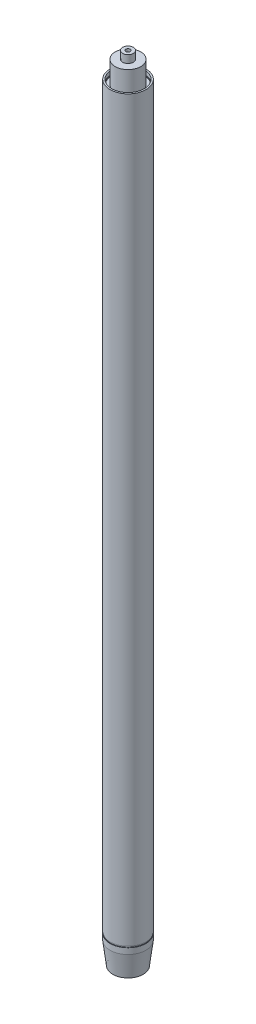
SolidWorks part; units mm, degrees
ref_plane "Front Plane" through (0, 0, 0) normal (0, 0, 1) x (1, 0, 0)
ref_plane "Top Plane" through (0, 0, 0) normal (0, 1, 0) x (1, 0, 0)
ref_plane "Right Plane" through (0, 0, 0) normal (1, 0, 0) x (0, 0, -1)
sketch "Sketch1" plane through (0, 0, 0) normal (0, 1, 0) x (1, 0, 0)
  circle A0 centre (0, 0) radius 26.7208
  circle A1 centre (0, 0) radius 24.3332
  dimension "D1" = 53.4416
  dimension "D2" = 2.3876
extrude "Boss-Extrude1" add sketch "Sketch1" along normal blind 1111.25
sketch "Sketch2" plane through (0, 0, 0) normal (0, 0, 1) x (1, 0, 0)
  line L0 (-26.7208, 0) -> (26.7208, 0) construction
  line L1 (22.5552, 7.112) -> (25.0952, 7.112)
  line L2 (22.5552, 7.112) -> (22.5552, 5.08)
  line L3 (22.5552, 5.08) -> (25.0952, 5.08)
  line L4 (25.0952, 7.112) -> (25.0952, 5.08)
  line L5 (24.3332, 0) -> (24.3332, 1111.25) construction
  dimension "D1" = 5.08
  dimension "D2" = 2.032
  dimension "D3" = 0.762
  dimension "D4" = 2.54
ref_axis "Axis1" through (0, 1111.25, 0) along (0, -1, 0)
revolve "Cut-Revolve1" cut sketch "Sketch2" angle 360 about axis through (0, 1111.25, 0) along (0, -1, 0)
ref_plane "Plane1" through (0, 555.625, 0) normal (0, -1, 0) x (-1, 0, 0)
mirror "Mirror1" about plane through (0, 555.625, 0) normal (0, -1, 0) of "Cut-Revolve1"
sketch "Sketch3" plane through (0, 0, 0) normal (1, 0, 0) x (0, 0, -1)
  line L0 (-26.7208, 0) -> (26.7208, 0) construction
  line L1 (25.9588, 10.795) -> (27.2288, 10.795)
  line L2 (25.9588, 10.795) -> (25.9588, 8.763)
  line L3 (25.9588, 8.763) -> (27.2288, 8.763)
  line L4 (27.2288, 10.795) -> (27.2288, 8.763)
  line L5 (26.7208, 0) -> (26.7208, 1111.25) construction
  dimension "D1" = 10.795
  dimension "D2" = 2.032
  dimension "D3" = 1.27
  dimension "D4" = 0.762
revolve "Cut-Revolve2" cut sketch "Sketch3" angle 360 about axis through (0, 1111.25, 0) along (0, -1, 0)
sketch "Sketch4" plane through (0, 0, 0) normal (0, 0, 1) x (1, 0, 0)
  line L0 (26.7208, 0) -> (22.6695, -33.147)
  line L1 (24.3332, 0) -> (20.2819, -33.147)
  line L2 (22.6695, -33.147) -> (20.2819, -33.147)
  line L3 (24.3332, 0) -> (26.7208, 0)
  dimension "D1" = 33.147
  dimension "D2" = 22.6695
revolve "Revolve2" add sketch "Sketch4" angle 360 about axis through (0, 1111.25, 0) along (0, -1, 0)
sketch "Sketch5" plane through (0, 1104.138, 0) normal (0, 1, 0) x (1, 0, 0)
  circle A0 centre (0, 0) radius 23.876
  dimension "D1" = 47.752
extrude "Boss-Extrude2" add sketch "Sketch5" against normal blind 12.7 separate body
sketch "Sketch6" plane through (0, 1104.138, 0) normal (0, 1, 0) x (1, 0, 0)
  circle A0 centre (0, 0) radius 19.05
  dimension "D1" = 38.1
extrude "Boss-Extrude4" add sketch "Sketch6" along normal blind 33.02 contours A0
sketch "Sketch7" plane through (0, 1137.158, 0) normal (0, 1, 0) x (1, 0, 0)
  circle A0 centre (0, 0) radius 7.9375
  circle A1 centre (0, 0) radius 3.175
  dimension "D1" = 6.35
  dimension "D2" = 15.875
extrude "Boss-Extrude5" add sketch "Sketch7" along normal blind 11.43
